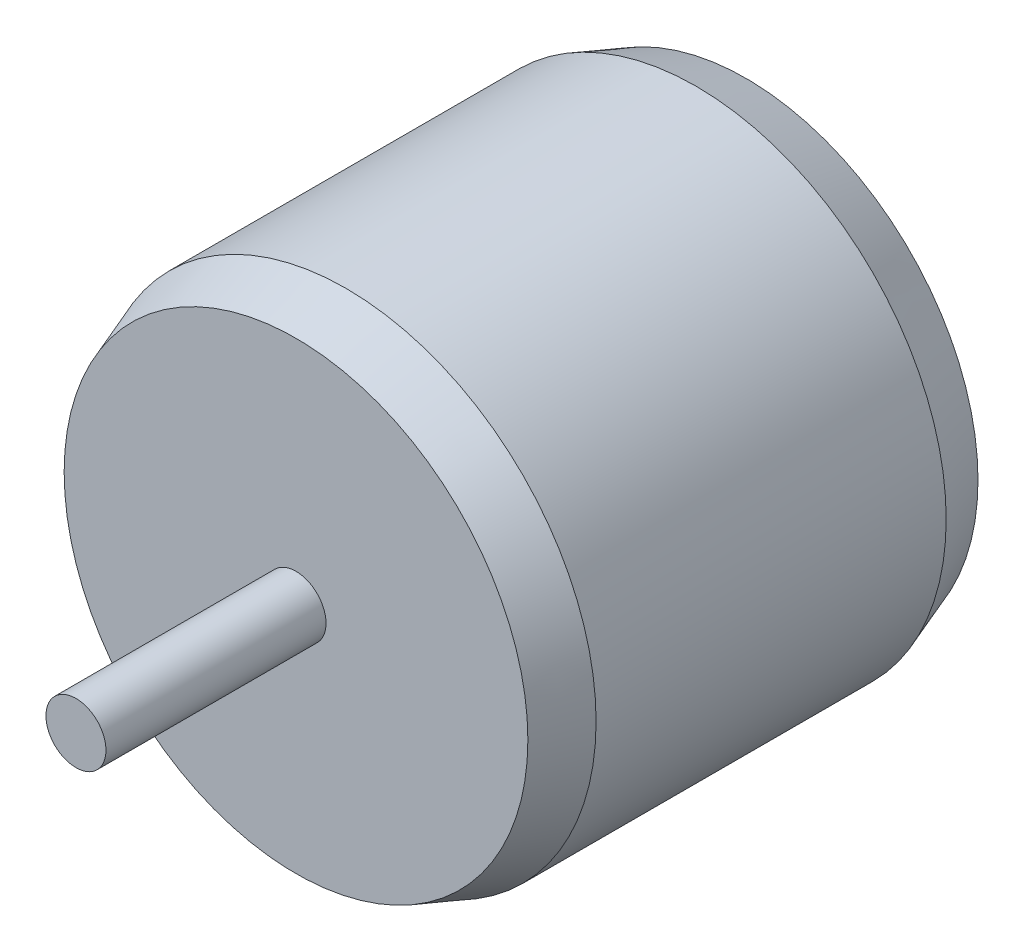
SolidWorks part; units mm, degrees
ref_plane "Front Plane" through (0, 0, 0) normal (0, 0, 1) x (1, 0, 0)
ref_plane "Top Plane" through (0, 0, 0) normal (0, 1, 0) x (1, 0, 0)
ref_plane "Right Plane" through (0, 0, 0) normal (1, 0, 0) x (0, 0, -1)
sketch "Sketch1" plane through (0, 0, 0) normal (0, 0, 1) x (1, 0, 0)
  circle A0 centre (0, 0) radius 25
  dimension "D1" = 50
extrude "Boss-Extrude1" add sketch "Sketch1" along normal blind 45
chamfer "Chamfer1" distance 5 angle 20 2 edges at (25, 0, 0) (25, 0, 45) first distance on face at (25, 0, 45)
sketch "Sketch2" plane through (0, 0, 45) normal (0, 0, 1) x (1, 0, 0)
  circle A0 centre (0, 0) radius 3
  dimension "D1" = 6
extrude "Boss-Extrude2" add sketch "Sketch2" along normal offset from surface (22 mm away) 67 up to face at (23.1801, 0, 0)
sketch "Sketch3" plane through (0, 0, 0) normal (0, 0, -1) x (-1, 0, 0)
  circle A0 centre (0, 0) radius 3
  dimension "D1" = 6
extrude "Boss-Extrude3" add sketch "Sketch3" along normal blind 2
